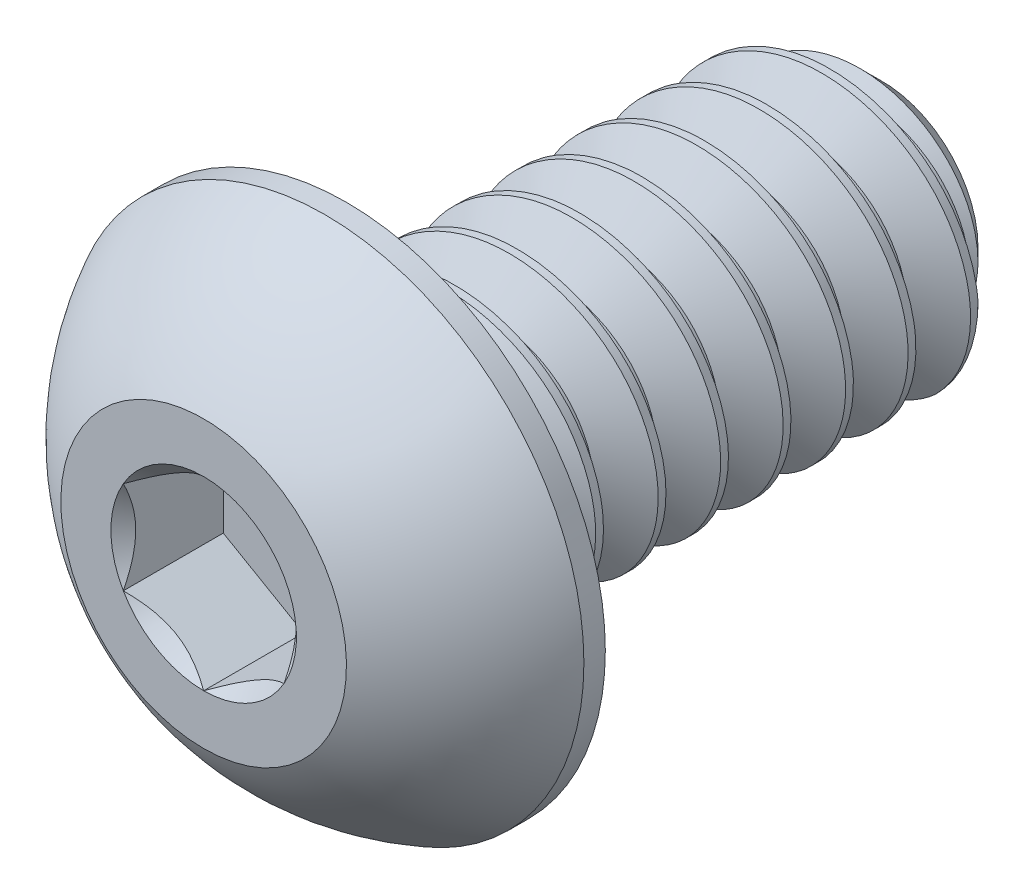
SolidWorks part; units mm, degrees
ref_plane "Front" through (0, 0, 0) normal (0, 0, 1) x (1, 0, 0)
ref_plane "Top" through (0, 0, 0) normal (0, 1, 0) x (1, 0, 0)
ref_plane "Right" through (0, 0, 0) normal (1, 0, 0) x (0, 0, -1)
sketch "Sketch1" plane through (0, 0, 0) normal (1, 0, 0) x (0, 0, -1)
  line L2 (0.8, 0.8) -> (3.8, 0.8)
  line L3 (3.8, 0.8) -> (3.8, 0)
  line L4 (3.8, 0) -> (0.8, 0)
  line L6 (0.68, 1.45) -> (0.8, 1.45) construction
  line L7 (3.8, 0.8) -> (3.8, -0.8) construction
  line L8 (0, 0) -> (0.8, 0) construction
  line L9 (0.8, 1.45) -> (0.8, -1.45) construction
  line L11 (0.8, 0.8) -> (0.8, 0)
  line L13 (0, 0.45) -> (0, -0.45) construction
  line L14 (0, 0.45) -> (0, 0.8) construction
  line L15 (3.7781, 0.8379) -> (3.9531, 0.5348) construction
  line L16 (3.9531, 0.5348) -> (4.1281, 0.8379) construction
  line L17 (4.1281, 0.8379) -> (3.7781, 0.8379) construction
  line L18 (3.8, 0.8) -> (4.1063, 0.8) construction
  line L19 (3.9531, 0.8379) -> (3.9531, 0.8) construction
  line L20 (3.9531, 0.8) -> (3.9531, 0.5727) construction
  line L21 (3.9531, 0.5727) -> (3.9531, 0.5348) construction
  line L22 (3.9312, 0.5727) -> (3.975, 0.5727)
  line L23 (3.7891, 0.8189) -> (4.1172, 0.8189)
  line L24 (3.975, 0.5727) -> (4.1172, 0.8189)
  line L25 (3.9312, 0.5727) -> (3.7891, 0.8189)
  line L26 (3.5375, 0.8) -> (3.8, 0.5375)
  arc A3 (0, 0.8) -> (0.68, 1.45) centre (1.4154, 0) cw construction
  point P29 (3.9531, 0.8189)
  point P30 (2.925, -0.8)
  dimension "D1" = 0.12
  dimension "Pitch" = 0.35
  dimension "D3" = 0.0437
  dimension "D2" = 0.2625
  dimension "D4" = 45
  dimension "D5" = 0.875
sketch "Sketch10" plane through (0, 0, 0) normal (1, 0, 0) x (0, 0, -1)
  line L0 (3.5375, 0.8) -> (3.8, 0.5375) construction
  line L1 (3.5375, 0.8) -> (3.8, 0.5375)
  line L4 (3.8, 0.8) -> (0.8, 0.8)
  line L5 (3.8, 0) -> (3.8, 0.8)
  line L6 (0.8, 0) -> (3.8, 0)
  line L7 (0.8, 0.8) -> (0.8, 0)
  line L8 (3.5375, 0.8) -> (0.8, 0.8)
  line L9 (3.8, 0) -> (3.8, 0.5375)
  line L10 (0.8, 0) -> (3.8, 0)
  line L11 (0.8, 0.8) -> (0.8, 0)
  dimension "D1" = 0
revolve "Revolve3" add sketch "Sketch10" angle 360 about L8
sketch "Sketch7" plane through (0, 0, 0) normal (1, 0, 0) x (0, 0, -1)
  line L6 (0.68, 1.45) -> (0.8, 1.45) construction
  line L8 (0, 0) -> (0.8, 0) construction
  line L11 (0.8, 1.45) -> (0.8, -1.45) construction
  line L12 (0.68, 1.45) -> (0.8, 1.45)
  line L13 (0, 0) -> (0.8, 0)
  line L14 (0, 0.45) -> (0, -0.45) construction
  line L15 (0.8, 1.45) -> (0.8, 0)
  line L16 (0, 0.8) -> (0, 0)
  arc A2 (0.68, 1.45) -> (0, 0.8) centre (1.4154, 0) ccw construction
  arc A3 (0.68, 1.45) -> (0, 0.8) centre (1.4154, 0) ccw
revolve "Revolve2" add sketch "Sketch7" angle 360 mid plane about L13
sketch "Sketch5" plane through (0, 0, 0) normal (0, 0, 1) x (1, 0, 0)
  line L1 (0.45, -0.2598) -> (0.45, 0.2598)
  line L2 (0.45, 0.2598) -> (0, 0.5196)
  line L3 (0, 0.5196) -> (-0.45, 0.2598)
  line L4 (-0.45, 0.2598) -> (-0.45, -0.2598)
  line L5 (-0.45, -0.2598) -> (0, -0.5196)
  line L6 (0, -0.5196) -> (0.45, -0.2598)
  circle A0 centre (0, 0) radius 0.45 construction
extrude "Cut-Extrude2" cut sketch "Sketch5" against normal blind 0.56
sketch "Sketch6" plane through (0, 0, 0) normal (0, 0, 1) x (1, 0, 0)
  circle A0 centre (0, 0) radius 0.5196
extrude "Cut-Extrude3" cut sketch "Sketch6" against normal blind 0.56 draft 45
sketch "Sketch9" plane through (0, 0, -0.8) normal (0, 0, -1) x (-1, 0, 0)
  circle A0 centre (0, 0) radius 0.8 construction
  circle A4 centre (0, 0) radius 0.8
split "Split1" bodies to split 113 resulting bodies 123 124 split by face at (1.45, 0, -0.8)
sketch "Sketch11" plane through (0, 0, -3.8) normal (0, 0, -1) x (-1, 0, 0)
  circle A0 centre (0, 0) radius 0.8 construction
  circle A1 centre (0, 0) radius 0.8
curve "Helix/Spiral1" pitch 0.35 height 3.8 radius 0.8 centre (0, 0, -3.8) axis (0, 0, 1) start towards (0, 1, 0)
sketch "Sketch12" plane through (0, 0, 0) normal (1, 0, 0) x (0, 0, -1)
  line L0 (3.9312, 0.5727) -> (3.975, 0.5727) construction
  line L1 (3.975, 0.5727) -> (4.1172, 0.8189) construction
  line L2 (3.7891, 0.8189) -> (4.1172, 0.8189) construction
  line L3 (3.9312, 0.5727) -> (3.7891, 0.8189) construction
  line L4 (3.9312, 0.5727) -> (3.975, 0.5727)
  line L5 (3.975, 0.5727) -> (4.1172, 0.8189)
  line L6 (3.7891, 0.8189) -> (4.1172, 0.8189)
  line L7 (3.9312, 0.5727) -> (3.7891, 0.8189)
sweep "Cut-Sweep2" cut profiles "Sketch12" path "Helix/Spiral1" align with end faces yes
extrude "Boss-Extrude1" add sketch "Sketch9" along normal blind 10 draft 45
equation "\"D1@Cut-Extrude2\" = \"Head Ht@Sketch1\" * .7"
equation "\"D1@Sketch1\" = \"Head Ht@Sketch1\" * .15"
equation "\"D1@Cut-Extrude3\" = \"D1@Cut-Extrude2\""
equation "\"D3@Sketch1\" = \"Pitch@Sketch1\" / 8"
equation "\"D2@Sketch1\"=\"Pitch@Sketch1\"*0.75"
equation "\"D3@Helix/Spiral1\" = \"Lg@Sketch1\" + \"Head Ht@Sketch1\""
equation "\"D4@Helix/Spiral1\"=\"pitch@sketch1\""
equation "\"D5@Sketch1\"=\"Pitch@Sketch1\"*2.5"
